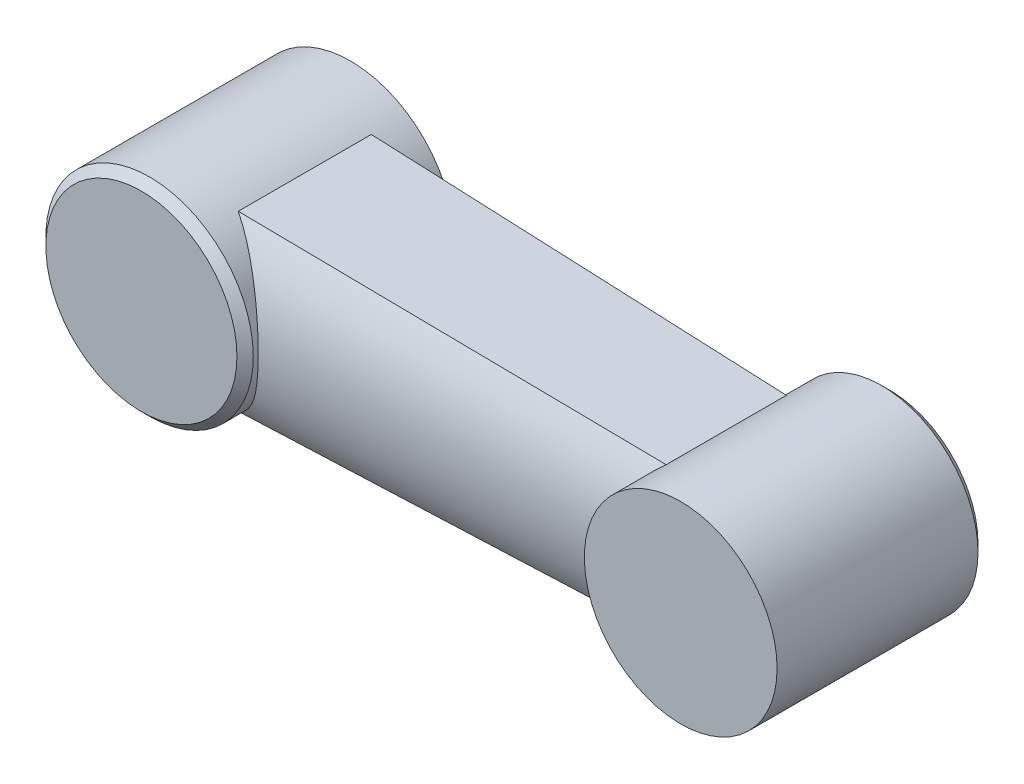
SolidWorks part; units mm, degrees
ref_plane "Front Plane" through (0, 0, 0) normal (0, 0, 1) x (1, 0, 0)
ref_plane "Top Plane" through (0, 0, 0) normal (0, 1, 0) x (1, 0, 0)
ref_plane "Right Plane" through (0, 0, 0) normal (1, 0, 0) x (0, 0, -1)
sketch "Sketch1" plane through (0, 0, 0) normal (0, 0, 1) x (1, 0, 0)
  circle A0 centre (0, 0) radius 63.5
  dimension "D1" = 127
extrude "Boss-Extrude1" add sketch "Sketch1" along normal blind 64 and the other way blind 64
chamfer "Chamfer1" distance 5 angle 45 1 edges at (63.5, 0, 64)
ref_plane "Plane2" through (63.5, 0, 0) normal (1, 0, 0) x (0, 0, -1)
ref_plane "Plane1" through (271.2, 0, 0) normal (1, 0, 0) x (0, 0, -1)
ref_plane "Plane3" through (330.2, 0, 0) normal (1, 0, 0) x (0, 0, -1)
ref_plane "Plane4" through (0, 0, 0) normal (0, 0, 1) x (1, 0, 0)
sketch "Sketch6" plane through (0, 0, 0) normal (-1, 0, 0) x (0, 0, 1)
  line L0 (-57.7088, 0) -> (57.7088, 0) construction
  line L6 (40.1204, -54) -> (-42.3796, -54)
  line L7 (-42.3796, 54) -> (40.1204, 54)
  arc A5 (-42.3796, 54) -> (-42.3796, -54) centre (45.0683, 0) ccw
  arc A6 (40.1204, 54) -> (40.1204, -54) centre (-33.9807, 0) cw
sketch "Sketch7" plane through (330.2, 0, 59) normal (-1, 0, 0) x (0, 0, 1)
  line L7 (-23.6711, -44.884) -> (-96.1377, -44.884)
  line L8 (-96.1377, 44.884) -> (-23.6711, 44.884)
  line L9 (-107.5928, 0) -> (-10.4072, 0) construction
  arc A11 (-96.1377, 44.884) -> (-96.1377, -44.884) centre (-13.9317, 0) ccw
  arc A12 (-23.6711, 44.884) -> (-23.6711, -44.884) centre (-92.9807, 0) cw
loft "Loft1" add profiles "Sketch6", "Sketch7" start constraint default end constraint default connector at (0, 54, 40.1204) connector at (330.2, 44.884, 35.3289)
sketch "Sketch9" plane through (0, 0, 0) normal (0, 0, 1) x (1, 0, 0)
  line L0 (330.2, -44.884) -> (330.2, 44.884) construction
  circle A0 centre (330.2, 0) radius 59
  dimension "D1" = 118
extrude "Boss-Extrude2" add sketch "Sketch9" along normal blind 64 and the other way blind 64
chamfer "Chamfer2" distance 5 angle 45 1 edges at (389.2, 0, -64)
ref_axis "Axis1" through (0, 0, 59) along (0, 0, -1)
ref_point "Point1"
